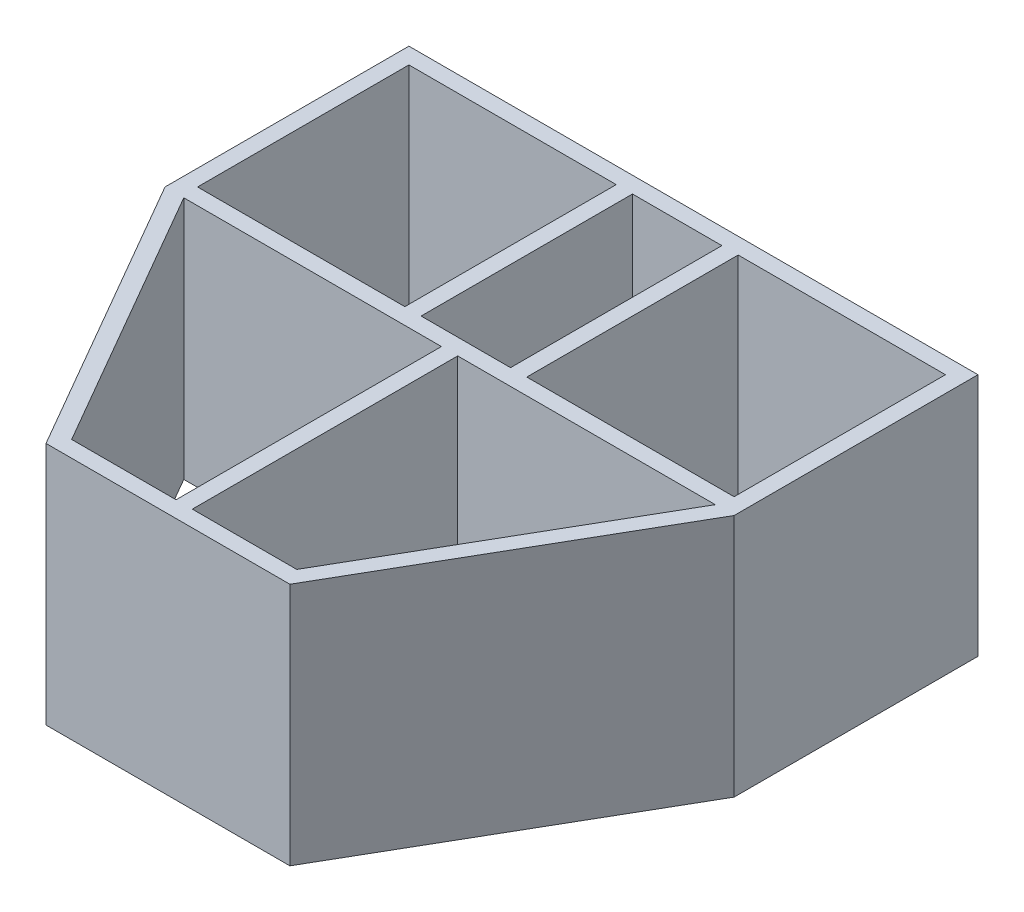
SolidWorks part; units mm, degrees
material "AISI 304"
ref_plane "前视基准面" through (0, 0, 0) normal (0, 0, 1) x (1, 0, 0)
ref_plane "上视基准面" through (0, 0, 0) normal (0, 1, 0) x (1, 0, 0)
ref_plane "右视基准面" through (0, 0, 0) normal (1, 0, 0) x (0, 0, -1)
ref_plane "InnerBottom" through (0, 0, 0) normal (0, 1, 0) x (1, 0, 0)
sketch "Circle" plane through (0, 0, 0) normal (0, 1, 0) x (1, 0, 0)
  line L0 (0, 0) -> (0, 200) construction
  dimension "R" = 200
ref_plane "InnerTop" through (0, 60, 0) normal (0, 1, 0) x (1, 0, 0)
ref_plane "SlotCenterV" through (0, 0, 0) normal (1, 0, 0) x (0, 0, -1)
ref_plane "SlotCenterH" through (0, 0, 0) normal (0, 0, 1) x (1, 0, 0)
ref_axis "CenterAxis" through (0, 0, -200) along (0, 1, 0)
sketch "STwoSlot" [suppressed] plane through (0, 0, 0) normal (0, 1, 0) x (1, 0, 0)
  line L0 (-32.1742, 0) -> (29.2905, 0) construction
  line L1 (0, 21.3687) -> (0, -19.6077) construction
  line L2 (-5, 4) -> (-5, -4)
  line L3 (-5, -4) -> (-7, -4)
  line L4 (-7, -4) -> (-7, -3)
  line L5 (-7, -3) -> (-10, -3)
  line L6 (-10, 3) -> (-7, 3)
  line L7 (-7, 3) -> (-7, 4)
  line L8 (-7, 4) -> (-5, 4)
  line L9 (5, -4) -> (7, -4)
  line L10 (7, -4) -> (7, -3)
  line L11 (7, -3) -> (10, -3)
  line L12 (10, 3) -> (7, 3)
  line L13 (7, 3) -> (7, 4)
  line L14 (7, 4) -> (5, 4)
  line L15 (5, 4) -> (5, -4)
  arc A0 (-10, -3) -> (-10, 3) centre (-10, 0) cw
  arc A1 (10, -3) -> (10, 3) centre (10, 0) ccw
  dimension "D4" = 3
  dimension "D1" = 8
  dimension "D2" = 2
  dimension "D3" = 3
  dimension "D5" = 10
sketch "STwoBase" [suppressed] plane through (0, 0, 0) normal (0, 1, 0) x (1, 0, 0)
  line L0 (0, 7.5) -> (0, -6.5) construction
  line L1 (-17.5, -7.5) -> (17.5, -7.5)
  line L2 (-17.5, -7.5) -> (-17.5, 7.5)
  line L3 (-17.5, 7.5) -> (17.5, 7.5)
  line L4 (17.5, -7.5) -> (17.5, 7.5)
  line L5 (-17.5, -7.5) -> (17.5, 7.5) construction
  line L6 (-17.5, 7.5) -> (17.5, -7.5) construction
  line L7 (-16.5, -6.5) -> (-0.5, -6.5)
  line L8 (-16.5, -6.5) -> (-16.5, 6.5)
  line L9 (-16.5, 6.5) -> (-0.5, 6.5)
  line L10 (16.5, -6.5) -> (16.5, 6.5)
  line L11 (-16.5, -6.5) -> (16.5, 6.5) construction
  line L12 (-16.5, 6.5) -> (16.5, -6.5) construction
  line L13 (-0.5, 6.5) -> (-0.5, -6.5)
  line L14 (0.5, 6.5) -> (0.5, -6.5)
  line L15 (0.5, 6.5) -> (16.5, 6.5)
  line L16 (0.5, -6.5) -> (16.5, -6.5)
  line L17 (0, 6.5) -> (0, -6.5) construction
  point P0 (0, 0)
  point P6 (0, 0)
  dimension "D1" = 35
  dimension "D5" = 1
  dimension "D2" = 15
  dimension "D3" = 1
  dimension "D4" = 1
extrude "FTwoBase" [suppressed] add sketch "STwoBase" along normal blind 15
sketch "SFiveSlotTP1" plane through (0, 0, 0) normal (0, 1, 0) x (1, 0, 0)
  line L0 (0, 21.9383) -> (0, -21.3523) construction
  line L1 (-37.6162, 0) -> (47.1378, 0) construction
  line L2 (-5.15, 11) -> (-5.15, 3)
  line L3 (-5.15, 3) -> (-7.55, 3)
  line L4 (-7.55, 3) -> (-7.55, 4)
  line L5 (-7.55, 4) -> (-10.55, 4)
  line L6 (-10.55, 10) -> (-7.55, 10)
  line L7 (-7.55, 10) -> (-7.55, 11)
  line L8 (-7.55, 11) -> (-5.15, 11)
  line L9 (-10.55, 7) -> (-5.15, 7) construction
  line L10 (7.55, 10) -> (7.55, 11)
  line L11 (10.55, 10) -> (7.55, 10)
  line L12 (7.55, 4) -> (10.55, 4)
  line L13 (7.55, 3) -> (7.55, 4)
  line L14 (5.15, 3) -> (7.55, 3)
  line L15 (5.15, 11) -> (5.15, 3)
  line L16 (7.55, 11) -> (5.15, 11)
  line L17 (-1.2, 7) -> (1.2, 7) construction
  line L18 (-1.2, 11.5) -> (1.2, 11.5)
  line L19 (-1.2, 11.5) -> (-1.2, 2.5)
  line L20 (-1.2, 2.5) -> (1.2, 2.5)
  line L21 (1.2, 11.5) -> (1.2, 2.5)
  line L22 (-7.2169, -4.1) -> (-2.7169, -11.8942)
  line L23 (-2.7169, -11.8942) -> (-4.7953, -13.0942)
  line L24 (-4.7953, -13.0942) -> (-9.2953, -5.3)
  line L25 (-9.2953, -5.3) -> (-7.2169, -4.1)
  line L26 (2.7169, -11.8942) -> (4.7953, -13.0942)
  line L27 (7.2169, -4.1) -> (2.7169, -11.8942)
  line L28 (4.7953, -13.0942) -> (9.2953, -5.3)
  line L29 (9.2953, -5.3) -> (7.2169, -4.1)
  line L30 (-8.2561, -4.7) -> (-3.7561, -12.4942) construction
  line L31 (-6.35, 11) -> (-6.35, 3) construction
  line L32 (6.35, 11) -> (6.35, 3) construction
  arc A0 (-10.55, 4) -> (-10.55, 10) centre (-10.55, 7) cw
  arc A1 (10.55, 4) -> (10.55, 10) centre (10.55, 7) ccw
  dimension "D4" = 3
  dimension "D1" = 8
  dimension "T3" = 2.4
  dimension "D3" = 3
  dimension "B1" = 9
  dimension "T1" = 2.4
  dimension "D7" = 7
  dimension "T2" = 2.4
  dimension "B2" = 9
  dimension "D12" = 60
  dimension "A" = 11.1
  dimension "F" = 9.5
  dimension "F2" = 12.7
sketch "SFiveBaseTP1" plane through (0, 0, 0) normal (0, 1, 0) x (1, 0, 0)
  line L0 (0, 29.2892) -> (0, -26.2802) construction
  line L1 (-17.5, 15) -> (17.5, 15)
  line L2 (17.5, 15) -> (17.5, 0)
  line L3 (17.5, 0) -> (7.5, -17.3205)
  line L4 (7.5, -17.3205) -> (-7.5, -17.3205)
  line L5 (-7.5, -17.3205) -> (-17.5, 0)
  line L6 (-17.5, 0) -> (-17.5, 15)
  line L8 (-16.3453, 0) -> (-6.9226, -16.3205)
  line L9 (-16.5, 14) -> (-3.75, 14)
  line L10 (-16.5, 14) -> (-16.5, 1)
  line L11 (-16.5, 1) -> (-3.75, 1)
  line L12 (16.5, 14) -> (16.5, 1)
  line L13 (-6.9226, -16.3205) -> (-0.5, -16.3205)
  line L14 (-0.5, -16.3205) -> (-0.5, 0)
  line L15 (-0.5, 0) -> (-16.3453, 0)
  line L16 (0.5, 0) -> (0.5, -16.3205)
  line L17 (0.5, -16.3205) -> (6.9226, -16.3205)
  line L18 (6.9226, -16.3205) -> (16.3453, 0)
  line L19 (16.3453, 0) -> (0.5, 0)
  line L20 (-3.75, 14) -> (-3.75, 1)
  line L21 (-2.75, 14) -> (-2.75, 1)
  line L22 (2.75, 14) -> (2.75, 1)
  line L23 (3.75, 14) -> (3.75, 1)
  line L24 (-2.75, 14) -> (2.75, 14)
  line L25 (3.75, 14) -> (16.5, 14)
  line L26 (-2.75, 1) -> (2.75, 1)
  line L27 (3.75, 1) -> (16.5, 1)
  dimension "D1" = 35
  dimension "D2" = 60
  dimension "D3" = 15
  dimension "D4" = 15
  dimension "D5" = 1
  dimension "D6" = 1
  dimension "D7" = 1
  dimension "D8" = 1
  dimension "D9" = 1
  dimension "D10" = 1
  dimension "D11" = 13
  dimension "D12" = 1
  dimension "D13" = 1
  dimension "D14" = 1
  dimension "D15" = 1
  dimension "D16" = 7.5
extrude "FFiveBaseTP1" add sketch "SFiveBaseTP1" along normal blind 15
sketch "SThreeSlot" [suppressed] plane through (0, 0, 0) normal (0, 1, 0) x (1, 0, 0)
  line L0 (-38.3697, 0) -> (49.7492, 0) construction
  line L1 (0, 31.5127) -> (0, -28.5949) construction
  line L2 (-9.2953, -5.3) -> (-4.7953, -13.0942)
  line L3 (-1.2, 11.5) -> (1.2, 11.5)
  line L4 (-1.2, 11.5) -> (-1.2, 2.5)
  line L5 (-1.2, 2.5) -> (1.2, 2.5)
  line L6 (1.2, 11.5) -> (1.2, 2.5)
  line L7 (-9.2953, -5.3) -> (-7.2169, -4.1)
  line L8 (-4.7953, -13.0942) -> (-2.7169, -11.8942)
  line L9 (-7.2169, -4.1) -> (-2.7169, -11.8942)
  line L10 (2.7169, -11.8942) -> (7.2169, -4.1)
  line L11 (2.7169, -11.8942) -> (4.7953, -13.0942)
  line L12 (7.2169, -4.1) -> (9.2953, -5.3)
  line L13 (4.7953, -13.0942) -> (9.2953, -5.3)
  line L14 (-1.2, 7) -> (1.2, 7) construction
  line L15 (-8.2561, -4.7) -> (-3.7561, -12.4942) construction
  dimension "B1" = 9
  dimension "T1" = 2.4
  dimension "T2" = 2.4
  dimension "B2" = 9
  dimension "F" = 9.5
  dimension "D1" = 60
  dimension "D2" = 11.1
  dimension "D3" = 7
sketch "SThreeBase" [suppressed] plane through (0, 0, 0) normal (0, 1, 0) x (1, 0, 0)
  line L0 (-19.047, 0) -> (-7.5, -20)
  line L1 (-7.5, -20) -> (7.5, -20)
  line L2 (7.5, -20) -> (19.047, 0)
  line L3 (19.047, 0) -> (5, 0)
  line L4 (5, 0) -> (5, 15)
  line L5 (5, 15) -> (-5, 15)
  line L6 (-5, 15) -> (-5, 0)
  line L7 (-19.047, 0) -> (-5, 0)
  line L8 (0, 24.0859) -> (0, -25.4306) construction
  line L9 (0, 31.5127) -> (0, -28.5949) construction
  line L11 (4, 0) -> (4, 14)
  line L12 (4, 14) -> (-4, 14)
  line L13 (-4, 14) -> (-4, 0)
  line L14 (-17.315, -1) -> (-4, -1)
  line L15 (-17.315, -1) -> (-6.9226, -19)
  line L16 (-6.9226, -19) -> (-0.5, -19)
  line L17 (6.9226, -19) -> (17.315, -1)
  line L18 (17.315, -1) -> (4, -1)
  line L19 (-4, -1) -> (-0.5, -1)
  line L20 (-4, 0) -> (4, 0)
  line L21 (-0.5, -1) -> (-0.5, -19)
  line L22 (-4, 14) -> (-4, -1) construction
  line L23 (4, -1) -> (4, 14) construction
  line L24 (0.5, -1) -> (0.5, -19)
  line L25 (0.5, -1) -> (4, -1)
  line L26 (0.5, -19) -> (6.9226, -19)
  line L28 (-6.9226, -19) -> (6.9226, -19) construction
  dimension "D3" = 15
  dimension "D6" = 1
  dimension "D7" = 1
  dimension "D2" = 15
  dimension "D1" = 10
  dimension "D4" = 20
  dimension "D5" = 60
extrude "FThreeBase" [suppressed] add sketch "SThreeBase" along normal blind 15
sketch "SUsbSlot" [suppressed] plane through (0, 0, 0) normal (0, 1, 0) x (1, 0, 0)
  line L0 (0, 4.2432) -> (0, -4.6578) construction
  line L2 (-2.5, -6) -> (2.5, -6)
  line L3 (-2.5, -6) -> (-2.5, 6)
  line L4 (-2.5, 6) -> (2.5, 6)
  line L5 (2.5, -6) -> (2.5, 6)
  line L6 (-2.5, -6) -> (2.5, 6) construction
  line L7 (-2.5, 6) -> (2.5, -6) construction
  point P3 (0, 0)
  dimension "UsbL" = 12
  dimension "UsbKd" = 5
sketch "SUsbBase" [suppressed] plane through (0, 0, 0) normal (0, 1, 0) x (1, 0, 0)
  line L1 (-5, -9) -> (5, -9)
  line L2 (-5, -9) -> (-5, 9)
  line L3 (-5, 9) -> (5, 9)
  line L4 (5, -9) -> (5, 9)
  line L5 (-5, -9) -> (5, 9) construction
  line L6 (-5, 9) -> (5, -9) construction
  line L7 (-4, 8) -> (4, 8)
  line L8 (4, -8) -> (4, 8)
  line L9 (-4, -8) -> (4, -8)
  line L10 (-4, -8) -> (-4, 8)
  dimension "D1" = 10
  dimension "D2" = 18
extrude "FUsbBase" [suppressed] add sketch "SUsbBase" along normal blind 15
equation "\"SlotL\"= 9"
equation "\"SlotKD\"= 2.4"
equation "\"B1@SFiveSlotTP1\"=\"SlotL\""
equation "\"B2@SFiveSlotTP1\"=\"SlotL\""
equation "\"T1@SFiveSlotTP1\"=\"SlotKD\""
equation "\"T3@SFiveSlotTP1\"=\"SlotKD\""
equation "\"T2@SFiveSlotTP1\"=\"SlotKD\""
equation "\"T1@SThreeSlot\"=\"SlotKD\""
equation "\"T2@SThreeSlot\"=\"SlotKD\""
equation "\"B1@SThreeSlot\"=\"SlotL\""
equation "\"B2@SThreeSlot\"=\"SlotL\""
equation "\"BaseTn\"=1"
equation "\"D5@SFiveBaseTP1\"=\"BaseTn\""
equation "\"D6@SFiveBaseTP1\"=\"BaseTn\""
equation "\"D7@SFiveBaseTP1\"=\"BaseTn\""
equation "\"D8@SFiveBaseTP1\"=\"BaseTn\""
equation "\"D9@SFiveBaseTP1\"=\"BaseTn\""
equation "\"D10@SFiveBaseTP1\"=\"BaseTn\""
equation "\"D12@SFiveBaseTP1\"=\"BaseTn\""
equation "\"D13@SFiveBaseTP1\"=\"BaseTn\""
equation "\"D5@STwoBase\"=\"BaseTn\""
equation "\"D3@STwoBase\"=\"BaseTn\""
equation "\"D4@STwoBase\"=\"BaseTn\""
equation "\"BaseH\"= 15"
equation "\"D1@FTwoBase\"=\"BaseH\""
equation "\"D1@FFiveBaseTP1\"=\"BaseH\""
equation "\"D6@SThreeBase\"=\"BaseTn\""
equation "\"D1@FThreeBase\"=\"BaseH\""
equation "\"D7@SThreeBase\"=\"BaseTn\""
equation "\"D3@SUsbBase\"=\"BaseTn\""
equation "\"D1@FUsbBase\"=\"BaseH\""
equation "\"D14@SFiveBaseTP1\"=\"BaseTn\""
equation "\"D15@SFiveBaseTP1\"=\"BaseTn\""
